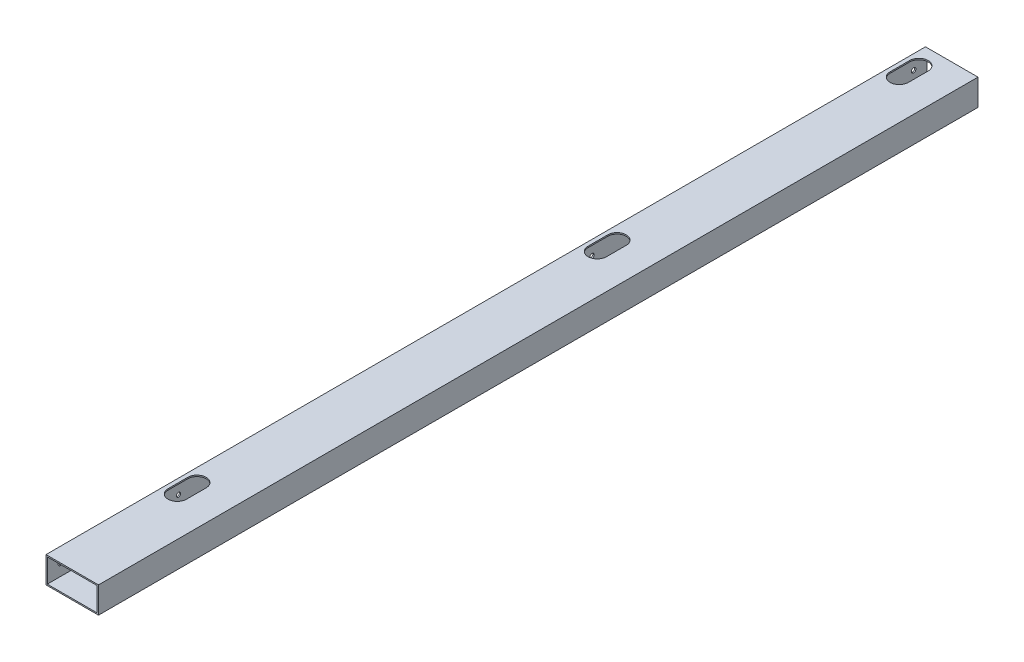
SolidWorks part; units mm, degrees
material "1060 合金"
ref_plane "前视基准面" through (0, 0, 0) normal (0, 0, 1) x (1, 0, 0)
ref_plane "上视基准面" through (0, 0, 0) normal (0, 1, 0) x (1, 0, 0)
ref_plane "右视基准面" through (0, 0, 0) normal (1, 0, 0) x (0, 0, -1)
other "Configuration Table"
sketch "草图1" plane through (0, 0, 0) normal (0, 0, 1) x (1, 0, 0)
  line L1 (0, 0) -> (40, 0)
  line L2 (0, 0) -> (0, -20)
  line L3 (0, -20) -> (40, -20)
  line L4 (40, 0) -> (40, -20)
  dimension "D1" = 20
  dimension "D2" = 40
extrude "拉伸-薄壁1" add sketch "草图1" along normal blind 670 thin thin type one direction reverse wall 1
sketch "草图4" plane through (0, 0, 0) normal (-1, 0, 0) x (0, 0, 1)
  line L0 (670, 0) -> (0, 0) construction
  line L1 (670, 0) -> (670, -20) construction
  line L4 (0, -180.2783) -> (0, 689.7217) construction
  circle A1 centre (659.9964, -10) radius 1.75
  circle A49 centre (10, -10) radius 1.75
  dimension "D27" = 3.5
  dimension "D28" = 3.5
  dimension "D29" = 10
  dimension "D25" = 10
  dimension "D26" = 10.0036
  dimension "D30" = 10
extrude "切除-拉伸2" cut sketch "草图4" against normal blind 1.5
sketch "草图5" plane through (0, 0, 0) normal (-1, 0, 0) x (0, 0, 1)
  circle A0 centre (42.5, -10) radius 1.75 construction
  circle A1 centre (42.5, -10) radius 1.75
  circle A2 centre (62.5, -10) radius 1.75
  circle A3 centre (82.5, -10) radius 1.75
  circle A4 centre (102.5, -10) radius 1.75
  circle A5 centre (122.5, -10) radius 1.75
  circle A6 centre (142.5, -10) radius 1.75
  circle A7 centre (162.5, -10) radius 1.75
  circle A8 centre (182.5, -10) radius 1.75
  circle A9 centre (202.5, -10) radius 1.75
  circle A10 centre (222.5, -10) radius 1.75
  circle A11 centre (242.5, -10) radius 1.75
  circle A12 centre (262.5, -10) radius 1.75
  circle A13 centre (282.5, -10) radius 1.75
  circle A14 centre (302.5, -10) radius 1.75
  circle A15 centre (322.5, -10) radius 1.75
  circle A16 centre (342.5, -10) radius 1.75
  circle A17 centre (362.5, -10) radius 1.75
  circle A18 centre (382.5, -10) radius 1.75
  circle A19 centre (402.5, -10) radius 1.75
  circle A20 centre (422.5, -10) radius 1.75
  circle A21 centre (442.5, -10) radius 1.75
  circle A22 centre (462.5, -10) radius 1.75
  circle A23 centre (482.5, -10) radius 1.75
  dimension "D1" = 23
sketch "草图6" plane through (40, 0, 0) normal (1, 0, 0) x (0, 0, -1)
  line L0 (-670, -20) -> (0, -20) construction
  line L1 (-670, -20) -> (-670, 0) construction
  circle A0 centre (-440, -10) radius 2.5
  circle A1 centre (-230, -10) radius 2.5
  dimension "D1" = 5
  dimension "D2" = 5
  dimension "D3" = 10
  dimension "D4" = 10
  dimension "D5" = 230
  dimension "D6" = 230
sketch "草图7" plane through (0, 0, 0) normal (-1, 0, 0) x (0, 0, 1)
  line L0 (670, -20) -> (0, -20) construction
  line L1 (0, 0) -> (0, -20) construction
  circle A0 centre (190, -10) radius 1.6
  circle A1 centre (170, -10) radius 1.6
  dimension "D1" = 3.2
  dimension "D2" = 3.2
  dimension "D3" = 10
  dimension "D4" = 10
  dimension "D5" = 170
  dimension "D6" = 20
sketch "草图8" plane through (0, 0, 0) normal (-1, 0, 0) x (0, 0, 1)
  line L0 (670, 0) -> (0, 0) construction
  line L1 (0, 0) -> (0, -20) construction
  circle A0 centre (45, -10) radius 1.65
  circle A1 centre (255, -10) radius 1.65
  dimension "D2" = 3.3
  dimension "D1" = 10
  dimension "D3" = 45
  dimension "D4" = 2
extrude "切除-拉伸3" cut sketch "草图8" against normal blind 5
sketch "草图9" plane through (0, 0, 0) normal (-1, 0, 0) x (0, 0, 1)
  line L0 (670, 0) -> (670, -20) construction
  line L1 (670, 0) -> (0, 0) construction
  circle A0 centre (570, -10) radius 1.6
  dimension "D2" = 3.2
  dimension "D1" = 100
  dimension "D3" = 10
extrude "切除-拉伸4" cut sketch "草图9" against normal blind 10
sketch "草图10" plane through (0, 0, 0) normal (0, 1, 0) x (1, 0, 0)
  line L0 (10, -580) -> (10, -565) construction
  line L1 (3, -580) -> (3, -565)
  line L2 (17, -580) -> (17, -565)
  line L3 (0, -670) -> (0, 0) construction
  line L4 (40, -670) -> (0, -670) construction
  line L5 (10, -30) -> (10, -15) construction
  line L6 (3, -30) -> (3, -15)
  line L7 (17, -30) -> (17, -15)
  arc A0 (3, -580) -> (17, -580) centre (10, -580) ccw
  arc A1 (17, -565) -> (3, -565) centre (10, -565) ccw
  arc A2 (3, -30) -> (17, -30) centre (10, -30) ccw
  arc A3 (17, -15) -> (3, -15) centre (10, -15) ccw
  point P2 (10, -572.5)
  point P15 (10, -22.5)
  dimension "D2" = 7
  dimension "D1" = 10
  dimension "D3" = 15
  dimension "D4" = 90
  dimension "D5" = 2
extrude "切除-拉伸5" cut sketch "草图10" against normal blind 10
pattern_linear "阵列(线性)1" count 2 spacing 230 along (0, 0, 1) of "切除-拉伸5"
